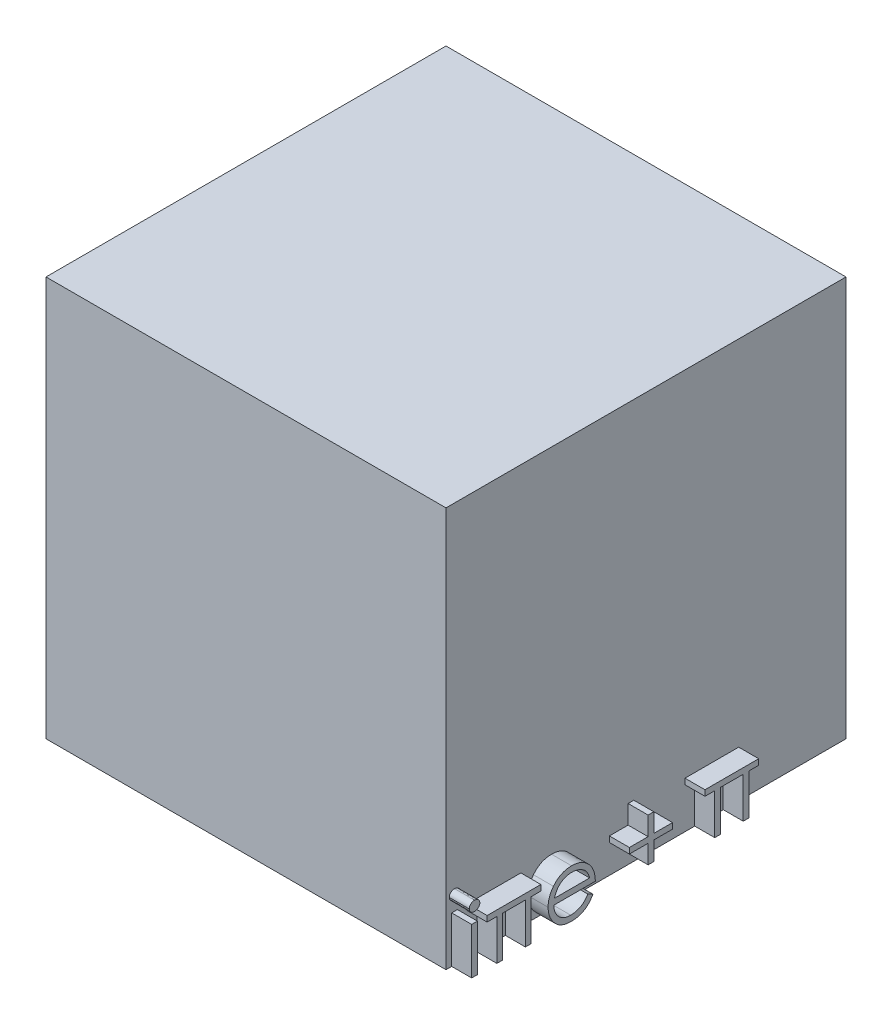
SolidWorks part; units mm, degrees
ref_plane "Front Plane" through (0, 0, 0) normal (0, 0, 1) x (1, 0, 0)
ref_plane "Top Plane" through (0, 0, 0) normal (0, 1, 0) x (1, 0, 0)
ref_plane "Right Plane" through (0, 0, 0) normal (1, 0, 0) x (0, 0, -1)
sketch "Sketch2" plane through (0, 0, 0) normal (0, 1, 0) x (1, 0, 0)
  line L1 (0, 0) -> (20, 0)
  line L2 (0, 0) -> (0, -20)
  line L3 (0, -20) -> (20, -20)
  line L4 (20, 0) -> (20, -20)
extrude "Boss-Extrude1" add sketch "Sketch2" along normal blind 20 contours L2 L3 L4 L1
sketch "Sketch3" plane through (20, 0, 0) normal (1, 0, 0) x (0, 0, -1)
  text T0 "iπe + π"
extrude "Boss-Extrude2" add sketch "Sketch3" along normal blind 1
